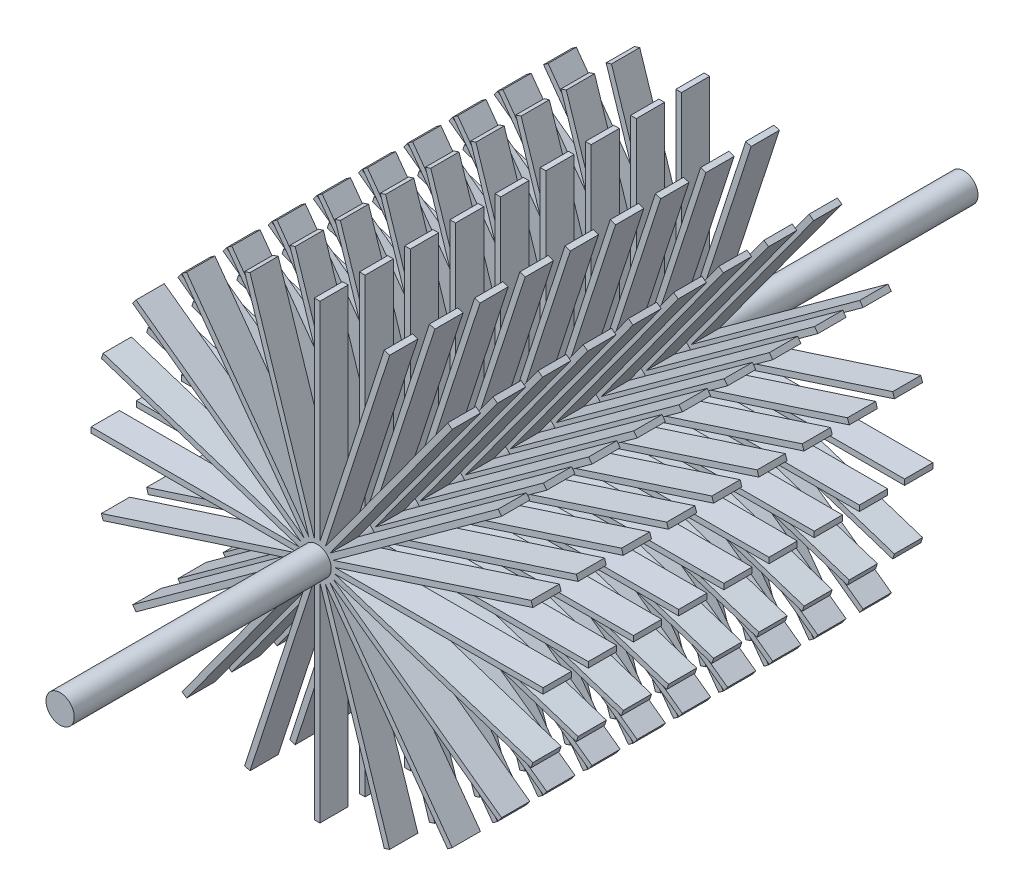
SolidWorks part; units mm, degrees
ref_plane "前视基准面" through (0, 0, 0) normal (0, 0, 1) x (1, 0, 0)
ref_plane "上视基准面" through (0, 0, 0) normal (0, 1, 0) x (1, 0, 0)
ref_plane "右视基准面" through (0, 0, 0) normal (1, 0, 0) x (0, 0, -1)
other "Configuration Table"
sketch "草图1" plane through (0, 0, 0) normal (0, 0, 1) x (1, 0, 0)
  circle A0 centre (0, 0) radius 2.5
  dimension "D1" = 5
extrude "凸台-拉伸1" add sketch "草图1" along normal mid plane 160
sketch "草图2" plane through (0, 0, 0) normal (0, 1, 0) x (1, 0, 0)
  line L1 (-0.5, 2.5) -> (0.5, 2.5)
  line L2 (-0.5, 2.5) -> (-0.5, -2.5)
  line L3 (-0.5, -2.5) -> (0.5, -2.5)
  line L4 (0.5, 2.5) -> (0.5, -2.5)
  line L5 (-0.5, 2.5) -> (0.5, -2.5) construction
  line L6 (-0.5, -2.5) -> (0.5, 2.5) construction
  point P0 (0, 0)
  dimension "D1" = 1
  dimension "D2" = 5
extrude "凸台-拉伸2" add sketch "草图2" along normal blind 40
pattern_circular "阵列(圆周)1" count 20 over 360 about axis through (0, 0, 80) along (0, 0, -1) of "凸台-拉伸2"
pattern_linear "阵列(线性)1" count 5 spacing 8 along (0, 0, -1) count 5 spacing 8 along (0, 0, 1) of "阵列(圆周)1" pattern seed only yes
